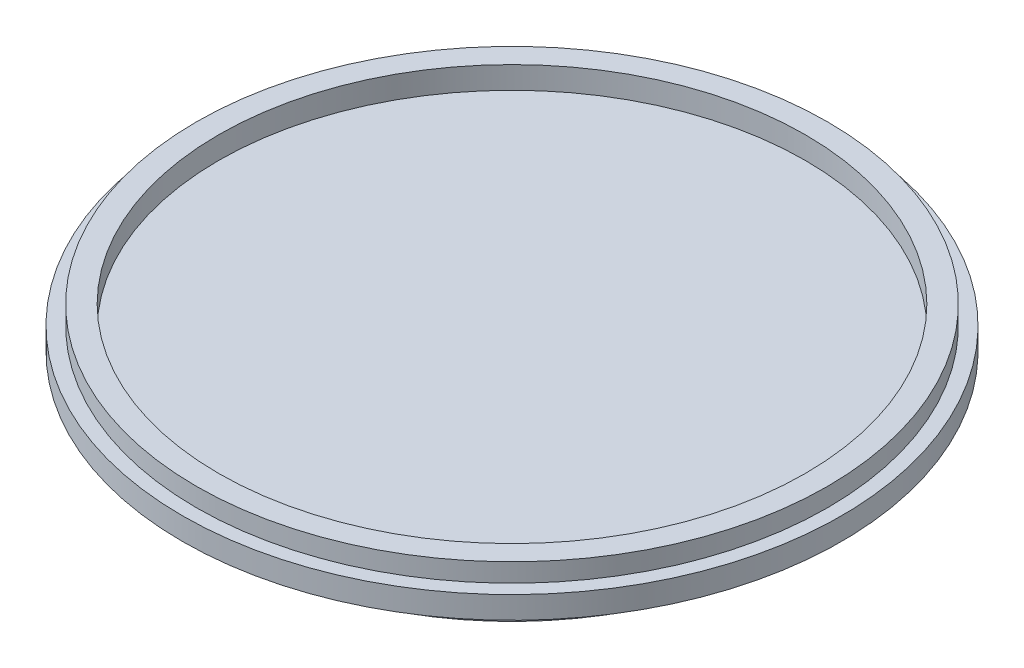
SolidWorks part; units mm, degrees
material "PC 高粘度"
ref_plane "前视基准面" through (0, 0, 0) normal (0, 0, 1) x (1, 0, 0)
ref_plane "上视基准面" through (0, 0, 0) normal (0, 1, 0) x (1, 0, 0)
ref_plane "右视基准面" through (0, 0, 0) normal (1, 0, 0) x (0, 0, -1)
sketch "草图1" plane through (0, 0, 0) normal (0, 1, 0) x (1, 0, 0)
  circle A0 centre (0, 0) radius 17
  circle A1 centre (0, 0) radius 15.8
extrude "凸台-拉伸1" add sketch "草图1" along normal blind 1
sketch "草图2" plane through (0, 0, 0) normal (0, -1, 0) x (1, 0, 0)
  circle A0 centre (0, 0) radius 17.75
  circle A1 centre (0, 0) radius 15.8
extrude "凸台-拉伸2" add sketch "草图2" along normal blind 1.2
sketch "草图3" plane through (0, -1.2, 0) normal (0, -1, 0) x (-1, 0, 0)
  circle A0 centre (0, 0) radius 16.75
  circle A1 centre (0, 0) radius 15.8
extrude "切除-拉伸1" cut sketch "草图3" against normal blind 0.5
sketch "草图4" plane through (0, -0.7, 0) normal (0, -1, 0) x (1, 0, 0)
  circle A0 centre (0, 0) radius 15.8
  circle A1 centre (0, 0) radius 15
extrude "凸台-拉伸3" add sketch "草图4" against normal blind 0.5 separate body
sketch "草图6" plane through (0, -0.2, 0) normal (0, 1, 0) x (1, 0, 0)
  circle A0 centre (0, 0) radius 15
extrude "凸台-拉伸4" add sketch "草图6" along direction (0, -1, 0) on the side against the normal blind 3
